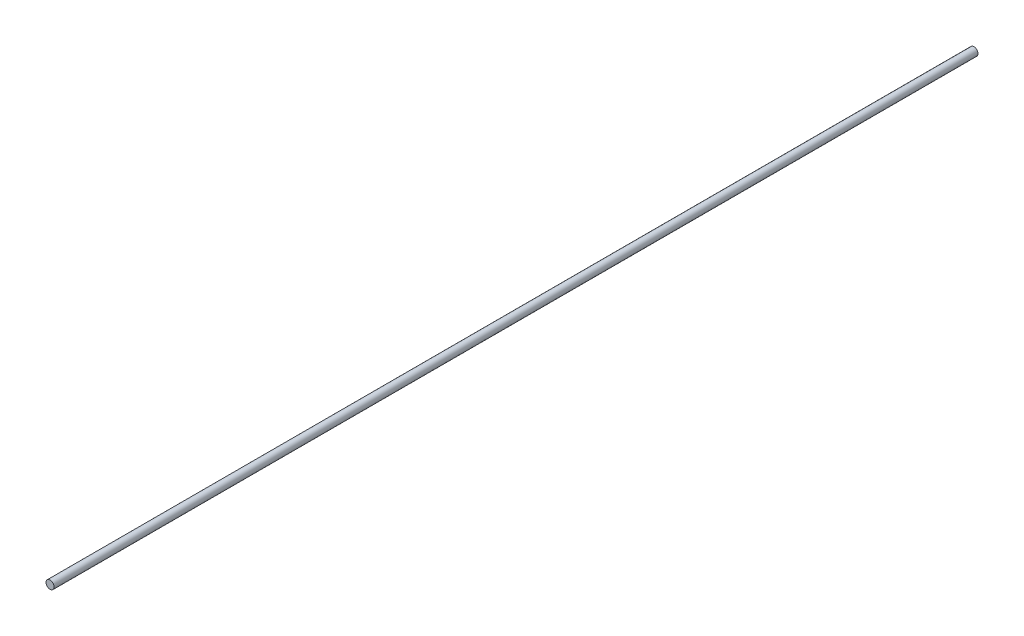
SolidWorks part; units mm, degrees
material "6061-T6 (SS)"
ref_plane "Front Plane" through (0, 0, 0) normal (0, 0, 1) x (1, 0, 0)
ref_plane "Top Plane" through (0, 0, 0) normal (0, 1, 0) x (1, 0, 0)
ref_plane "Right Plane" through (0, 0, 0) normal (1, 0, 0) x (0, 0, -1)
sketch "Sketch1" plane through (0, 0, 0) normal (0, 0, 1) x (1, 0, 0)
  line L1 (-4, 0) -> (4, 0) construction
  dimension "OD" = 8
sketch "Sketch2" plane through (0, 0, 0) normal (1, 0, 0) x (0, 0, -1)
  line L0 (457.2, 0) -> (-457.2, 0)
  point P4 (0, 0)
  dimension "Length" = 914.4
sketch "Sketch3" plane through (0, 0, 0) normal (0, 0, 1) x (1, 0, 0)
  circle A0 centre (0, 0) radius 4
extrude "Boss-Extrude1" add sketch "Sketch3" along normal up to vertex (457.2 mm away) and the other way up to vertex (457.2 mm away) up to point (0, 0, 457.2) other way up to point (0, 0, -457.2)
